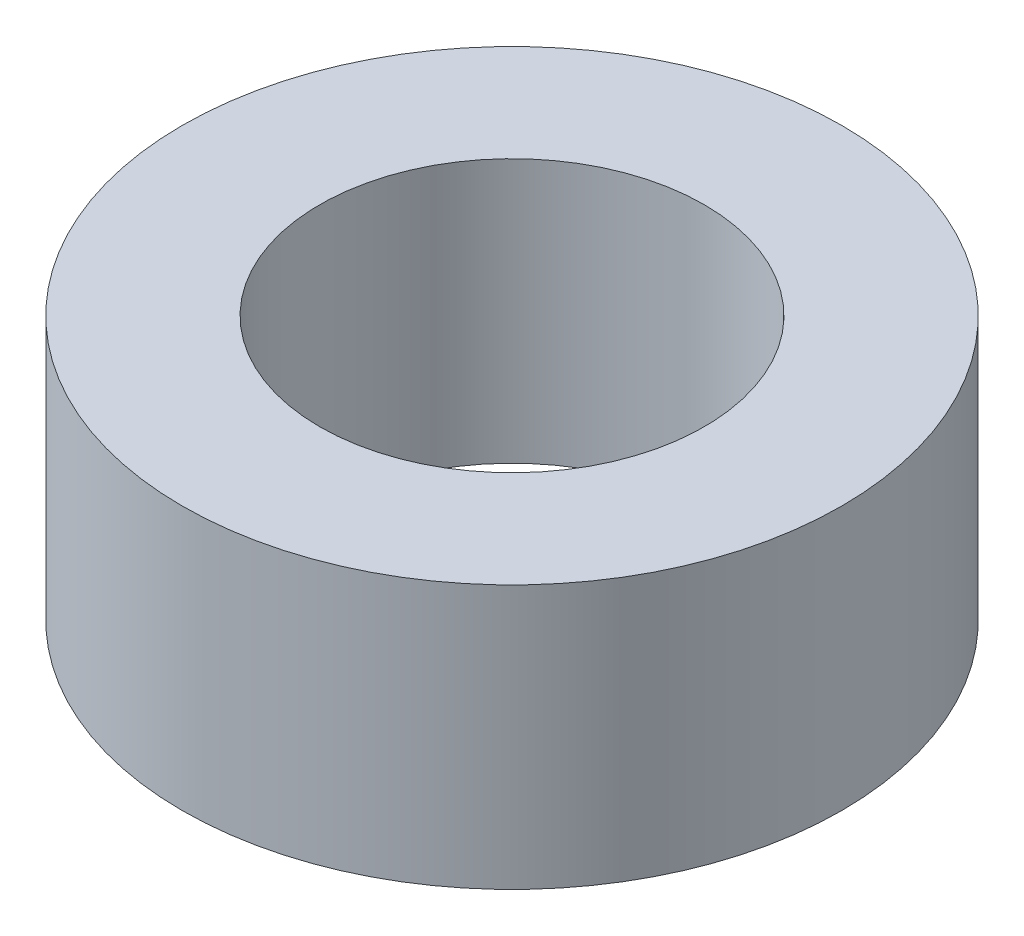
SolidWorks part; units mm, degrees
ref_plane "Front Plane" through (0, 0, 0) normal (0, 0, 1) x (1, 0, 0)
ref_plane "Top Plane" through (0, 0, 0) normal (0, 1, 0) x (1, 0, 0)
ref_plane "Right Plane" through (0, 0, 0) normal (1, 0, 0) x (0, 0, -1)
sketch "Sketch1" plane through (0, 0, 0) normal (0, 1, 0) x (1, 0, 0)
  circle A0 centre (0, 0) radius 30
  dimension "FLANGE_OD" = 60
extrude "Boss-Extrude1" add sketch "Sketch1" along normal blind 24
sketch "Sketch2" plane through (0, 0, 0) normal (0, 1, 0) x (1, 0, 0)
  circle A0 centre (0, 0) radius 17.5
  dimension "BORE_D" = 35
extrude "Cut-Extrude1" cut sketch "Sketch2" along normal through all
sketch "Sketch3" plane through (0, 24, 0) normal (0, 1, 0) x (1, 0, 0)
  circle A0 centre (0, 0) radius 10.9023 construction
  circle A1 centre (-10.9023, 0) radius 1.8426
  dimension "BOLT_D" = 3.6852
  dimension "BOLT_PCD" = 21.8046
extrude "Cut-Extrude2" cut sketch "Sketch3" against normal blind 18.1533 rebuild error yes
pattern_circular "CirPattern1" count 8 over 360 rebuild error yes
